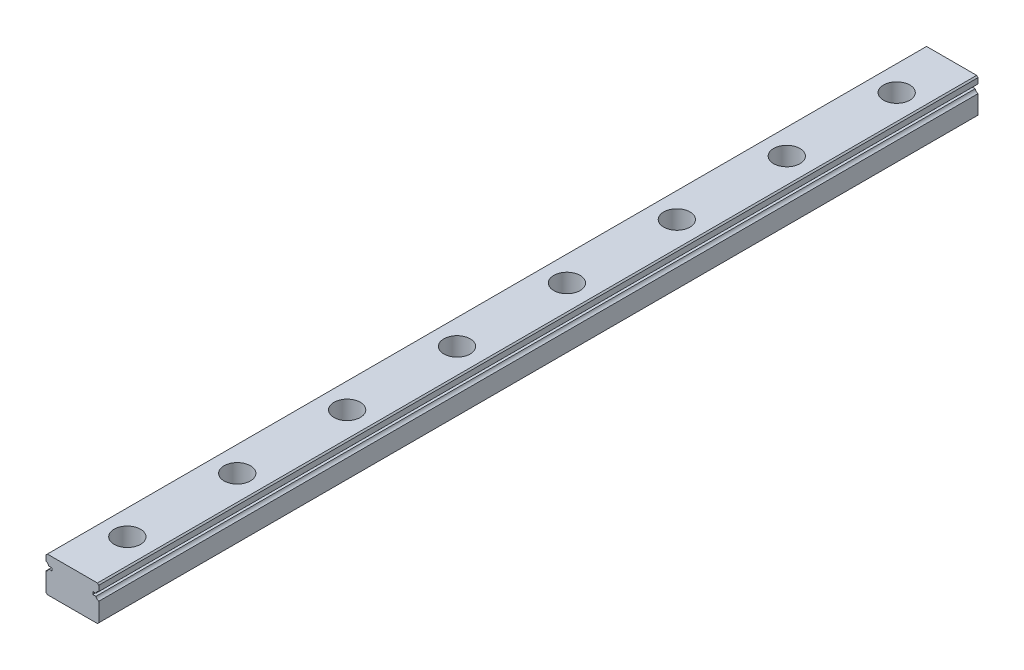
SolidWorks part; units mm, degrees
ref_plane "Спереди" through (0, 0, 0) normal (0, 0, 1) x (1, 0, 0)
ref_plane "Сверху" through (0, 0, 0) normal (0, 1, 0) x (1, 0, 0)
ref_plane "Справа" through (0, 0, 0) normal (1, 0, 0) x (0, 0, -1)
sketch "Эскиз1" plane through (0, 0, 0) normal (0, 0, 1) x (1, 0, 0)
  line L0 (-6, 3.7) -> (-5.7, 4)
  line L1 (-5.7, -4) -> (5.7, -4)
  line L2 (-6, -3.7) -> (-6, 0.549)
  line L3 (-5.7, 4) -> (5.7, 4)
  line L4 (6, -3.7) -> (6, 0.549)
  line L5 (-6, -4) -> (6, 4) construction
  line L6 (-6, 4) -> (6, -4) construction
  line L7 (-6, -3.7) -> (-5.7, -4)
  line L8 (5.7, -4) -> (6, -3.7)
  line L9 (5.7, 4) -> (6, 3.7)
  line L10 (-6, 2.451) -> (-6, 3.7)
  line L11 (-5.3546, 1.7981) -> (-4.6435, 1.7981)
  line L12 (0, 5.4188) -> (0, -5.747) construction
  line L13 (-5.3546, 1.2019) -> (-4.6435, 1.2019)
  line L14 (-4.6435, 1.7981) -> (-4.6435, 1.2019)
  line L15 (4.6435, 1.7981) -> (4.6435, 1.2019)
  line L16 (5.3546, 1.2019) -> (4.6435, 1.2019)
  line L17 (5.3546, 1.7981) -> (4.6435, 1.7981)
  line L18 (6, 2.451) -> (6, 3.7)
  line L19 (4.6435, 1.7981) -> (5.3546, 1.7981) construction
  arc A0 (-6, 0.549) -> (-5.3546, 1.2019) centre (-6.3091, 1.5) ccw
  arc A1 (-5.3546, 1.7981) -> (-6, 2.451) centre (-6.3091, 1.5) ccw
  arc A2 (5.3546, 1.7981) -> (6, 2.451) centre (6.3091, 1.5) cw
  arc A3 (6, 0.549) -> (5.3546, 1.2019) centre (6.3091, 1.5) cw
  point P0 (0, 0)
extrude "Бобышка-Вытянуть1" add sketch "Эскиз1" along normal blind 200
sketch "Эскиз2" plane through (0, 4, 0) normal (0, 1, 0) x (1, 0, 0)
  line L0 (0, 0) -> (0, -26.2396) construction
  line L1 (5.7, 0) -> (-5.7, 0) construction
  line L2 (-3.8306, -12.5) -> (3.8306, -12.5) construction
  circle A0 centre (0, -12.5) radius 3
  circle A1 centre (0, -12.5) radius 1.75
  dimension "D2" = 3.5
  dimension "D3" = 6
  dimension "D1" = 12.5
extrude "Вырез-Вытянуть1" cut sketch "Эскиз2" against normal blind 4.5
extrude "Вырез-Вытянуть2" cut sketch "Эскиз2<2>" against normal through all contours A1 region at (0, 4, 12.5)
sketch "Эскиз2<2>" plane through (0, 4, 0) normal (0, 1, 0) x (1, 0, 0) same geometry as "Эскиз2"
pattern_linear "Линейный массив1" count 10 spacing 25 along (0, 0, 1) of "Вырез-Вытянуть1", "Вырез-Вытянуть2"
